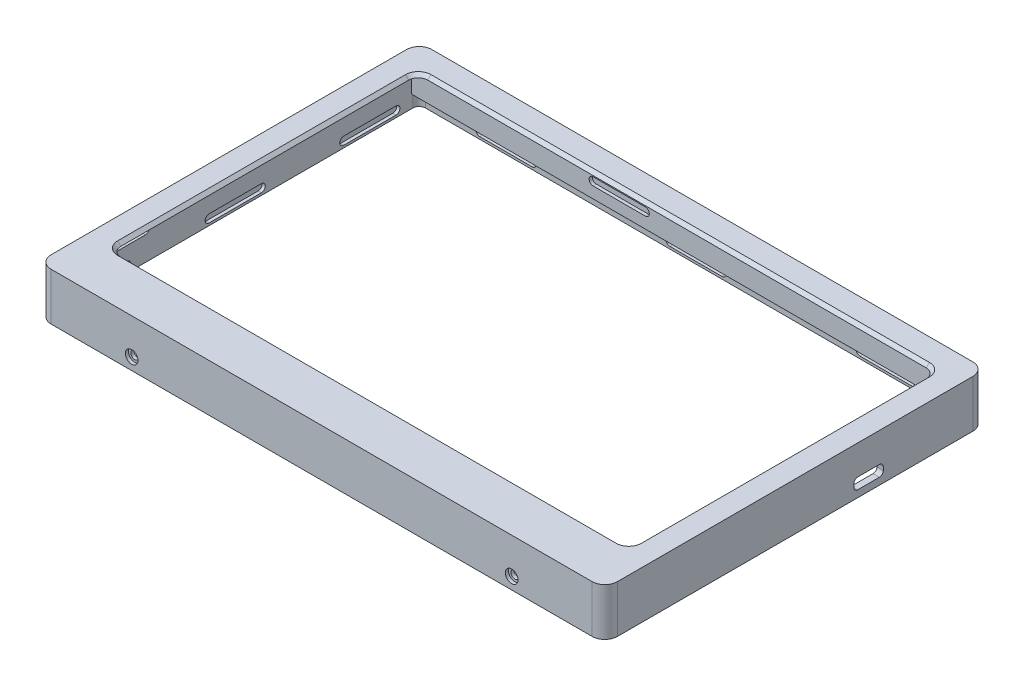
SolidWorks part; units mm, degrees
ref_plane "前基準面" through (0, 0, 0) normal (0, 0, 1) x (1, 0, 0)
ref_plane "上基準面" through (0, 0, 0) normal (0, 1, 0) x (1, 0, 0)
ref_plane "右基準面" through (0, 0, 0) normal (1, 0, 0) x (0, 0, -1)
sketch "草圖1" plane through (0, 0, 0) normal (0, 1, 0) x (1, 0, 0)
  line L1 (-89.4, 60.1) -> (89.4, 60.1)
  line L2 (-89.4, 60.1) -> (-89.4, -60.1)
  line L3 (-89.4, -60.1) -> (89.4, -60.1)
  line L4 (89.4, 60.1) -> (89.4, -60.1)
  line L5 (-89.4, 60.1) -> (89.4, -60.1) construction
  line L6 (-89.4, -60.1) -> (89.4, 60.1) construction
  point P0 (0, 0)
  dimension "D1" = 120.2
  dimension "D2" = 178.8
extrude "填料-伸長1" add sketch "草圖1" along normal blind 16
shell "薄殼1" thickness 2 removed face at (0, 0, 0)
sketch "草圖4" plane through (0, 16, 0) normal (0, 1, 0) x (1, 0, 0)
  line L0 (89.4, 60.1) -> (-89.4, 60.1) construction
  line L1 (-89.4107, 60.1) -> (89.4107, 60.1)
  line L2 (-89.4107, 60.1) -> (-89.4107, -60.1)
  line L3 (-89.4107, -60.1) -> (89.4107, -60.1)
  line L4 (89.4107, 60.1) -> (89.4107, -60.1)
  line L5 (-89.4107, 60.1) -> (89.4107, -60.1) construction
  line L6 (-89.4107, -60.1) -> (89.4107, 60.1) construction
  point P0 (0, 0)
extrude "除料-伸長2" cut sketch "草圖4" against normal blind 1
sketch "草圖2" plane through (0, 15, 0) normal (0, 1, 0) x (1, 0, 0)
  line L1 (-81.7, 52.1) -> (81.7, 52.1)
  line L2 (-81.7, 52.1) -> (-81.7, -44.82)
  line L3 (-81.7, -44.82) -> (81.7, -44.82)
  line L4 (81.7, 52.1) -> (81.7, -44.82)
  line L5 (-81.7, 52.1) -> (81.7, -44.82) construction
  line L6 (-81.7, -44.82) -> (81.7, 52.1) construction
  line L7 (0, 60.1) -> (0, -60.1) construction
  line L9 (89.4, 60.1) -> (-89.4, 60.1) construction
  line L10 (-89.4, -60.1) -> (89.4, -60.1) construction
  point P0 (0, 3.64)
  dimension "D1" = 8
  dimension "D2" = 163.4
  dimension "D3" = 96.92
extrude "除料-伸長1" cut sketch "草圖2" against normal up to surface (1 mm away) up to face at (0, 14, 0)
fillet "圓角2" radius 3 4 edges at (81.7, 14.5, -52.1) (81.7, 14.5, 44.82) (-81.7, 14.5, 44.82) (-81.7, 14.5, -52.1)
chamfer "導角1" distance 1 angle 45 8 edges at (0, 15, 44.82) (80.8213, 15, 43.9413) (-80.8213, 15, 43.9413) (81.7, 15, -3.64) (-81.7, 15, -3.64) (80.8213, 15, -51.2213) (-80.8213, 15, -51.2213) (0, 15, -52.1)
sketch "草圖13" plane through (0, 14, 0) normal (0, -1, 0) x (1, 0, 0)
  line L1 (-87.4, 58.1) -> (-15, 58.1)
  line L2 (-87.4, 58.1) -> (-87.4, -58.1)
  line L3 (-87.4, -58.1) -> (87.4, -58.1)
  line L4 (87.4, 58.1) -> (87.4, -58.1)
  line L5 (-87.4, 58.1) -> (87.4, -58.1) construction
  line L6 (-87.4, -58.1) -> (87.4, 58.1) construction
  line L8 (87.4, 58.1) -> (87.4, -58.1) construction
  line L9 (87.4, -58.1) -> (-87.4, -58.1) construction
  line L10 (15, 58.1) -> (15, 55.965)
  line L11 (85.325, -55.705) -> (-85.325, -55.705)
  line L12 (85.325, -55.705) -> (85.325, 55.965)
  line L13 (85.325, 55.965) -> (15, 55.965)
  line L14 (-85.325, -55.705) -> (-85.325, 55.965)
  line L15 (85.325, -55.705) -> (-85.325, 55.965) construction
  line L16 (85.325, 55.965) -> (-85.325, -55.705) construction
  line L17 (0, 58.1) -> (0, 55.65) construction
  line L18 (-15, 58.1) -> (-15, 55.965)
  line L19 (15, 58.1) -> (87.4, 58.1)
  line L20 (-15, 55.965) -> (-85.325, 55.965)
  point P0 (0, 0)
  point P24 (0, 0.13)
  dimension "D2" = 170.65
  dimension "D3" = 111.67
  dimension "D4" = 58.23
  dimension "D5" = 15
extrude "填料-伸長2" add sketch "草圖13" along normal blind 1
sketch "Sketch1" plane through (0, 0, -58.1) normal (0, 0, 1) x (1, 0, 0)
  line L0 (-89.4, 15) -> (89.4, 15)
  line L1 (89.4, 15) -> (89.4, 4)
  line L3 (-89.4, 4) -> (-89.4, 15)
  line L4 (-89.4, 4) -> (89.4, 4)
  line L5 (89.4, 0) -> (-89.4, 0) construction
  dimension "D1" = 4
extrude "Boss-Extrude1" add sketch "Sketch1" along normal up to surface (2.395 mm away) up to face at (0, 13.5, -55.705)
ref_plane "平面1" through (0, 0, 0) normal (0, 0, 1) x (1, 0, 0)
ref_plane "平面2" through (0, 0, 0) normal (-1, 0, 0) x (0, 0, 1)
fillet "圓角1" radius 4 4 edges at (89.4, 7.5, -60.1) (89.4, 7.5, 60.1) (-89.4, 7.5, 60.1) (-89.4, 7.5, -60.1)
sketch "草圖5" plane through (0, 0, -55.705) normal (0, 0, 1) x (1, 0, 0)
  line L0 (-85.4, 15) -> (85.4, 15) construction
  line L1 (-11.85, 6.81) -> (-31.85, 6.81)
  line L2 (-11.85, 6.81) -> (-11.85, 10.81)
  line L3 (-11.85, 10.81) -> (-31.85, 10.81)
  line L4 (-31.85, 6.81) -> (-31.85, 10.81)
  line L5 (-31.85, 8.81) -> (-11.85, 8.81) construction
  line L6 (-30.1, 8.81) -> (-13.6, 8.81) construction
  line L7 (-30.1, 10.06) -> (-13.6, 10.06)
  line L8 (-30.1, 7.56) -> (-13.6, 7.56)
  arc A0 (-30.1, 10.06) -> (-30.1, 7.56) centre (-30.1, 8.81) ccw
  arc A1 (-13.6, 7.56) -> (-13.6, 10.06) centre (-13.6, 8.81) ccw
  point P12 (-21.85, 8.81)
  dimension "D1" = 11.85
  dimension "D2" = 4.19
  dimension "D3" = 4
  dimension "D4" = 20
  dimension "D5" = 16.5
  dimension "D6" = 2.5
extrude "除料-伸長3" cut sketch "草圖5" against normal blind 1 contours L8 A1 L7 A0 | L8 A0 L7 A1 region at (-21.85, 8.81, -55.705)
sketch "草圖6" plane through (-87.4, 0, 0) normal (1, 0, 0) x (0, 0, -1)
  line L0 (-56.1, 15) -> (56.1, 15) construction
  line L1 (-26.64, 6.81) -> (-46.64, 6.81)
  line L2 (-26.64, 6.81) -> (-26.64, 10.81)
  line L3 (-26.64, 10.81) -> (-46.64, 10.81)
  line L4 (-46.64, 6.81) -> (-46.64, 10.81)
  line L5 (-26.64, 8.81) -> (-46.64, 8.81) construction
  line L6 (-28.39, 8.81) -> (-44.89, 8.81) construction
  line L7 (-28.39, 7.56) -> (-44.89, 7.56)
  line L8 (-28.39, 10.06) -> (-44.89, 10.06)
  line L9 (0, 0) -> (0, 15) construction
  line L10 (28.39, 11.75) -> (44.89, 11.75) construction
  line L11 (28.39, 10.5) -> (44.89, 10.5)
  line L12 (28.39, 13) -> (44.89, 13)
  arc A0 (-28.39, 7.56) -> (-28.39, 10.06) centre (-28.39, 8.81) ccw
  arc A1 (-44.89, 10.06) -> (-44.89, 7.56) centre (-44.89, 8.81) ccw
  arc A2 (28.39, 10.5) -> (28.39, 13) centre (28.39, 11.75) cw
  arc A3 (44.89, 13) -> (44.89, 10.5) centre (44.89, 11.75) cw
  point P10 (-36.64, 8.81)
  point P20 (36.64, 11.75)
  dimension "D1" = 4.19
  dimension "D2" = 20
  dimension "D3" = 4
  dimension "D4" = 16.5
  dimension "D5" = 2.5
  dimension "D6" = 26.64
  dimension "D7" = 2.5
  dimension "D8" = 3.25
extrude "除料-伸長4" cut sketch "草圖6" against normal blind 1 contours L8 A1 L7 A0 region at (-87.4, 8.81, 36.64)
mirror "Mirror4" about plane through (0, 0, 0) normal (-1, 0, 0) of "除料-伸長4"
extrude "Cut-Extrude1" cut sketch "草圖6<4>" against normal blind 1 contours A3 L12 A2 L11 region at (-87.4, 11.75, -36.64)
sketch "草圖6<4>" plane through (-87.4, 0, 0) normal (1, 0, 0) x (0, 0, -1) same geometry as "草圖6"
mirror "Mirror2" about plane through (0, 0, 0) normal (-1, 0, 0) of "Cut-Extrude1"
sketch "草圖7" plane through (0, 0, 58.1) normal (0, 0, -1) x (-1, 0, 0)
  line L0 (-85.4, 15) -> (85.4, 15) construction
  line L1 (-57.03, 10.81) -> (-37.03, 10.81)
  line L2 (-57.03, 10.81) -> (-57.03, 6.81)
  line L3 (-57.03, 6.81) -> (-37.03, 6.81)
  line L4 (-37.03, 10.81) -> (-37.03, 6.81)
  line L5 (-57.03, 8.81) -> (-37.03, 8.81) construction
  line L6 (-55.28, 8.81) -> (-38.78, 8.81) construction
  line L7 (-55.28, 10.06) -> (-38.78, 10.06)
  line L8 (-55.28, 7.56) -> (-38.78, 7.56)
  line L9 (0, 0) -> (0, 15) construction
  line L10 (-57.03, 10.81) -> (-37.03, 10.81)
  line L11 (-57.03, 6.81) -> (-37.03, 6.81)
  line L12 (57.03, 8.81) -> (37.03, 8.81) construction
  line L13 (57.03, 6.81) -> (37.03, 6.81)
  line L14 (57.03, 10.81) -> (37.03, 10.81)
  line L15 (37.03, 10.81) -> (37.03, 6.81)
  line L16 (57.03, 6.81) -> (37.03, 6.81)
  line L17 (57.03, 10.81) -> (57.03, 6.81)
  line L18 (57.03, 10.81) -> (37.03, 10.81)
  line L19 (55.28, 8.81) -> (38.78, 8.81) construction
  line L20 (55.28, 10.06) -> (38.78, 10.06)
  line L21 (55.28, 7.56) -> (38.78, 7.56)
  arc A0 (-55.28, 10.06) -> (-55.28, 7.56) centre (-55.28, 8.81) ccw
  arc A1 (-38.78, 7.56) -> (-38.78, 10.06) centre (-38.78, 8.81) ccw
  arc A2 (55.28, 10.06) -> (55.28, 7.56) centre (55.28, 8.81) cw
  arc A3 (38.78, 7.56) -> (38.78, 10.06) centre (38.78, 8.81) cw
  point P4 (-37.03, 8.81)
  point P12 (-47.03, 8.81)
  point P27 (47.03, 8.81)
  dimension "D1" = 20
  dimension "D2" = 4
  dimension "D3" = 37.03
  dimension "D4" = 4.19
  dimension "D5" = 16.5
  dimension "D6" = 2.5
extrude "除料-伸長5" cut sketch "草圖7" against normal blind 1 contours L8 A1 L7 A0 | A3 L21 A2 L20 region at (47.03, 8.81, 58.1) region at (-47.03, 8.81, 58.1)
sketch "草圖9" plane through (89.4, 0, 0) normal (1, 0, 0) x (0, 0, -1)
  line L1 (26.59, 2.18) -> (19.79, 2.18)
  line L2 (27.84, 3.43) -> (27.84, 4.43)
  line L3 (26.59, 5.68) -> (19.79, 5.68)
  line L4 (18.54, 3.43) -> (18.54, 4.43)
  line L5 (27.84, 2.18) -> (18.54, 5.68) construction
  line L6 (27.84, 5.68) -> (18.54, 2.18) construction
  line L8 (60.1, 15) -> (60.1, 0) construction
  line L9 (-56.1, 15) -> (56.1, 15) construction
  arc A0 (19.79, 5.68) -> (18.54, 4.43) centre (19.79, 4.43) ccw
  arc A1 (19.79, 2.18) -> (18.54, 3.43) centre (19.79, 3.43) cw
  arc A2 (26.59, 2.18) -> (27.84, 3.43) centre (26.59, 3.43) ccw
  arc A3 (27.84, 4.43) -> (26.59, 5.68) centre (26.59, 4.43) ccw
  point P0 (23.19, 3.93)
  dimension "D5" = 1.25
  dimension "D1" = 36.91
  dimension "D2" = 11.07
  dimension "D3" = 9.3
  dimension "D4" = 3.5
extrude "除料-伸長7" cut sketch "草圖9" against normal up to next
sketch "草圖11" plane through (0, 0, -58.1) normal (0, 0, 1) x (1, 0, 0)
  line L0 (-8.25, 2) -> (8.25, 2) construction
  line L1 (-8.25, 3.25) -> (8.25, 3.25)
  line L2 (-8.25, 0.75) -> (8.25, 0.75)
  line L3 (-85.4, 0) -> (85.4, 0) construction
  line L4 (51.75, 2) -> (68.25, 2) construction
  line L5 (51.75, 3.25) -> (68.25, 3.25)
  line L6 (51.75, 0.75) -> (68.25, 0.75)
  line L7 (-68.25, 2) -> (-51.75, 2) construction
  line L8 (-68.25, 3.25) -> (-51.75, 3.25)
  line L9 (-68.25, 0.75) -> (-51.75, 0.75)
  arc A0 (-8.25, 3.25) -> (-8.25, 0.75) centre (-8.25, 2) ccw
  arc A1 (8.25, 0.75) -> (8.25, 3.25) centre (8.25, 2) ccw
  arc A2 (51.75, 3.25) -> (51.75, 0.75) centre (51.75, 2) ccw
  arc A3 (68.25, 0.75) -> (68.25, 3.25) centre (68.25, 2) ccw
  arc A4 (-68.25, 3.25) -> (-68.25, 0.75) centre (-68.25, 2) ccw
  arc A5 (-51.75, 0.75) -> (-51.75, 3.25) centre (-51.75, 2) ccw
  point P2 (0, 2)
  point P13 (60, 2)
  point P20 (-60, 2)
  dimension "D1" = 16.5
  dimension "D2" = 2.5
  dimension "D3" = 2
  dimension "D4" = 2
  dimension "D5" = 2
extrude "除料-伸長9" cut sketch "草圖11" against normal blind 1 contours L2 A1 L1 A0 region at (0, 2, -58.1)
extrude "Cut-Extrude3" cut sketch "草圖11<3>" against normal blind 1 contours L6 A3 L5 A2 | L9 A5 L8 A4 region at (60, 2, -58.1) region at (-60, 2, -58.1)
sketch "草圖11<3>" plane through (0, 0, -58.1) normal (0, 0, 1) x (1, 0, 0) same geometry as "草圖11"
sketch "草圖12" plane through (-87.4, 0, 0) normal (1, 0, 0) x (0, 0, -1)
  line L0 (-8.25, 2) -> (8.25, 2) construction
  line L1 (-8.25, 3.25) -> (8.25, 3.25)
  line L2 (-8.25, 0.75) -> (8.25, 0.75)
  line L3 (-56.1, 0) -> (56.1, 0) construction
  line L4 (34.25, 2) -> (50.75, 2) construction
  line L5 (34.25, 3.25) -> (50.75, 3.25)
  line L6 (34.25, 0.75) -> (50.75, 0.75)
  line L7 (-50.75, 2) -> (-34.25, 2) construction
  line L8 (-50.75, 3.25) -> (-34.25, 3.25)
  line L9 (-50.75, 0.75) -> (-34.25, 0.75)
  arc A0 (-8.25, 3.25) -> (-8.25, 0.75) centre (-8.25, 2) ccw
  arc A1 (8.25, 0.75) -> (8.25, 3.25) centre (8.25, 2) ccw
  arc A2 (34.25, 3.25) -> (34.25, 0.75) centre (34.25, 2) ccw
  arc A3 (50.75, 0.75) -> (50.75, 3.25) centre (50.75, 2) ccw
  arc A4 (-50.75, 3.25) -> (-50.75, 0.75) centre (-50.75, 2) ccw
  arc A5 (-34.25, 0.75) -> (-34.25, 3.25) centre (-34.25, 2) ccw
  point P2 (0, 2)
  point P13 (42.5, 2)
  point P19 (-42.5, 2)
  dimension "D1" = 16.5
  dimension "D2" = 2.5
  dimension "D3" = 2
  dimension "D6" = 42.5
  dimension "D7" = 42.5
  dimension "D4" = 2
  dimension "D5" = 2
extrude "除料-伸長10" cut sketch "草圖12" against normal blind 1
mirror "鏡射2" about plane through (0, 0, 0) normal (-1, 0, 0) of "除料-伸長10"
sketch "Sketch3" plane through (0, 0, -55.705) normal (0, 0, 1) x (1, 0, 0)
  line L0 (51.9003, 11.75) -> (68.4003, 11.75) construction
  line L1 (51.9003, 13) -> (68.4003, 13)
  line L2 (51.9003, 10.5) -> (68.4003, 10.5)
  line L3 (51.75, 2) -> (68.25, 2) construction
  line L5 (85.4, 15) -> (-85.4, 15) construction
  arc A0 (51.9003, 13) -> (51.9003, 10.5) centre (51.9003, 11.75) ccw
  arc A1 (68.4003, 10.5) -> (68.4003, 13) centre (68.4003, 11.75) ccw
  point P2 (60.1503, 11.75)
  dimension "D1" = 2.5
  dimension "D2" = 3.25
extrude "Cut-Extrude2" cut sketch "Sketch3" against normal blind 1
fillet "Fillet1" radius 2 4 edges at (-87.4, 6.5, 58.1) (87.4, 6.5, 58.1) (-87.4, 2, -58.1) (87.4, 2, -58.1)
sketch "Sketch4" plane through (0, 0, 60.1) normal (0, 0, 1) x (1, 0, 0)
  line L0 (-85.4, 0) -> (85.4, 0) construction
  circle A0 centre (60, 3.75) radius 2
  circle A1 centre (60, 3.75) radius 1.25
  dimension "D1" = 4
  dimension "D4" = 2.5
  dimension "D2" = 3.75
  dimension "D3" = 60
extrude "Cut-Extrude4" cut sketch "Sketch4" against normal blind 1 contours A1 | A0 A1 region at (58.0566, 3.75, 60.1) region at (60, 3.75, 60.1)
extrude "Cut-Extrude5" cut sketch "Sketch4<3>" against normal up to surface (2 mm away) contours A1 region at (60, 3.75, 60.1) up to face at (47.03, 8.81, 58.1)
sketch "Sketch4<3>" plane through (0, 0, 60.1) normal (0, 0, 1) x (1, 0, 0) same geometry as "Sketch4"
mirror "Mirror3" about plane through (0, 0, 0) normal (-1, 0, 0) of "Cut-Extrude5", "Cut-Extrude4"
sketch "Sketch5" plane through (0, 0, 58.1) normal (0, 0, -1) x (-1, 0, 0)
  line L0 (27, 2) -> (43.5, 2) construction
  line L1 (27, 3.25) -> (43.5, 3.25)
  line L2 (27, 0.75) -> (43.5, 0.75)
  line L3 (0, 0) -> (0, 15) construction
  line L4 (85.4, 0) -> (-85.4, 0) construction
  line L5 (85.4, 15) -> (-85.4, 15) construction
  line L6 (-85.4, 0) -> (85.4, 0) construction
  line L7 (-27, 2) -> (-43.5, 2) construction
  line L8 (-27, 3.25) -> (-43.5, 3.25)
  line L9 (-27, 0.75) -> (-43.5, 0.75)
  arc A0 (27, 3.25) -> (27, 0.75) centre (27, 2) ccw
  arc A1 (43.5, 0.75) -> (43.5, 3.25) centre (43.5, 2) ccw
  arc A2 (-27, 3.25) -> (-27, 0.75) centre (-27, 2) cw
  arc A3 (-43.5, 0.75) -> (-43.5, 3.25) centre (-43.5, 2) cw
  point P2 (35.25, 2)
  point P17 (-35.25, 2)
  dimension "D1" = 2.5
  dimension "D2" = 16.5
  dimension "D3" = 35.25
  dimension "D4" = 2
extrude "Cut-Extrude6" cut sketch "Sketch5" against normal blind 1
equation "\"ㄉ\"=4"
equation "\"ㄉ0\"=21"
equation "\"ㄉㄢ\"=21"
